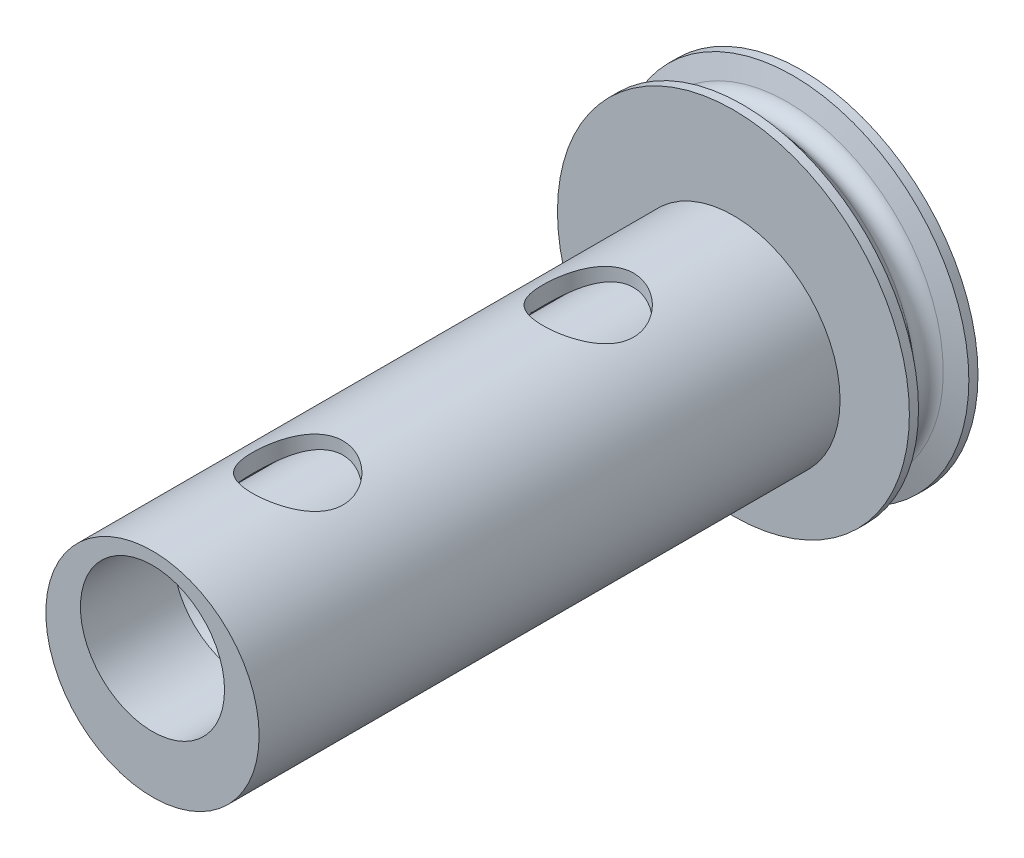
SolidWorks part; units mm, degrees
material "ABS"
ref_plane "Front Plane" through (0, 0, 0) normal (0, 0, 1) x (1, 0, 0)
ref_plane "Top Plane" through (0, 0, 0) normal (0, 1, 0) x (1, 0, 0)
ref_plane "Right Plane" through (0, 0, 0) normal (1, 0, 0) x (0, 0, -1)
sketch "Sketch1" plane through (0, 0, 0) normal (0, 0, 1) x (1, 0, 0)
  circle A0 centre (0, 1.938) radius 6.3
  circle A1 centre (0, 0) radius 9.525 construction
  circle A2 centre (0, 0) radius 9.525 construction
  circle A3 centre (0, 0) radius 9.325
  point P3 (0, 0)
  dimension "D1" = 12.6
  dimension "D3" = 0.2
  dimension "D2" = 1.938
extrude "Boss-Extrude1" add sketch "Sketch1" against normal up to surface (50.8 mm away)
ref_axis "Axis1" through (0, 1.938, -50.8) along (0, 0, 1)
sketch "Sketch3" plane through (0, 0, 0) normal (1, 0, 0) x (0, 0, -1)
  line L0 (50.8, 8.238) -> (50.8, 17.325)
  line L1 (50.8, 17.325) -> (51.6, 17.325)
  line L2 (51.6, 17.325) -> (53.4649, 15.1025)
  line L3 (55.527, 15.5597) -> (56, 17.325)
  line L4 (56, 17.325) -> (56.8, 17.325)
  line L5 (56.8, 17.325) -> (56.8, 9.296)
  line L6 (50.8, -9.325) -> (50.8, 9.325) construction
  line L9 (50.8, 9.325) -> (0, 9.325) construction
  line L10 (50.8, 8.238) -> (56.8, 9.296)
  line L11 (50.8, 8.238) -> (0, 8.238) construction
  arc A0 (53.4649, 15.1025) -> (55.527, 15.5597) centre (54.3769, 15.8679) ccw
  point P0 (51.7644, 5)
  point P16 (25.4, 9.325)
  dimension "D1" = 50
  dimension "D3" = 1.1906
  dimension "D2" = 0.8
  dimension "D4" = 8
  dimension "D5" = 75
  dimension "D6" = 6
  dimension "D8" = 80
revolve "Revolve1" add sketch "Sketch3" angle 360 about axis through (0, 1.938, -50.8) along (0, 0, 1)
ref_plane "Plane1" through (0, 0, -28.4) normal (0, 0, 1) x (1, 0, 0)
ref_plane "Plane2" through (0, 0, -54.3769) normal (0, 0, 1) x (1, 0, 0)
ref_plane "Plane3" through (0, 0, -25.4) normal (0, 0, 1) x (1, 0, 0)
sketch "Sketch7" plane through (0, 0, -25.4) normal (0, 0, 1) x (1, 0, 0)
  circle A0 centre (0, 1.938) radius 5
  circle A1 centre (0, 1.938) radius 6.2
  dimension "D1" = 10
extrude "Boss-Extrude2" add sketch "Sketch7" along normal offset from surface 8 and the other way offset from surface 8 up to face at (6.3, 1.938, 0) other way up to face at (9.325, 0, -50.8)
chamfer "Chamfer1" distance 1.2 angle 45 2 edges at (5, 1.938, -42.8) (5, 1.938, -8)
sketch "Sketch8" plane through (0, 0, 0) normal (0, 1, 0) x (1, 0, 0)
  circle A0 centre (0, 38.1) radius 3.9688
  circle A1 centre (0, 12.7) radius 3.9688
  point P4 (0, 12.7)
  dimension "D1" = 7.9375
extrude "Cut-Extrude3" cut sketch "Sketch8" along normal blind 26
